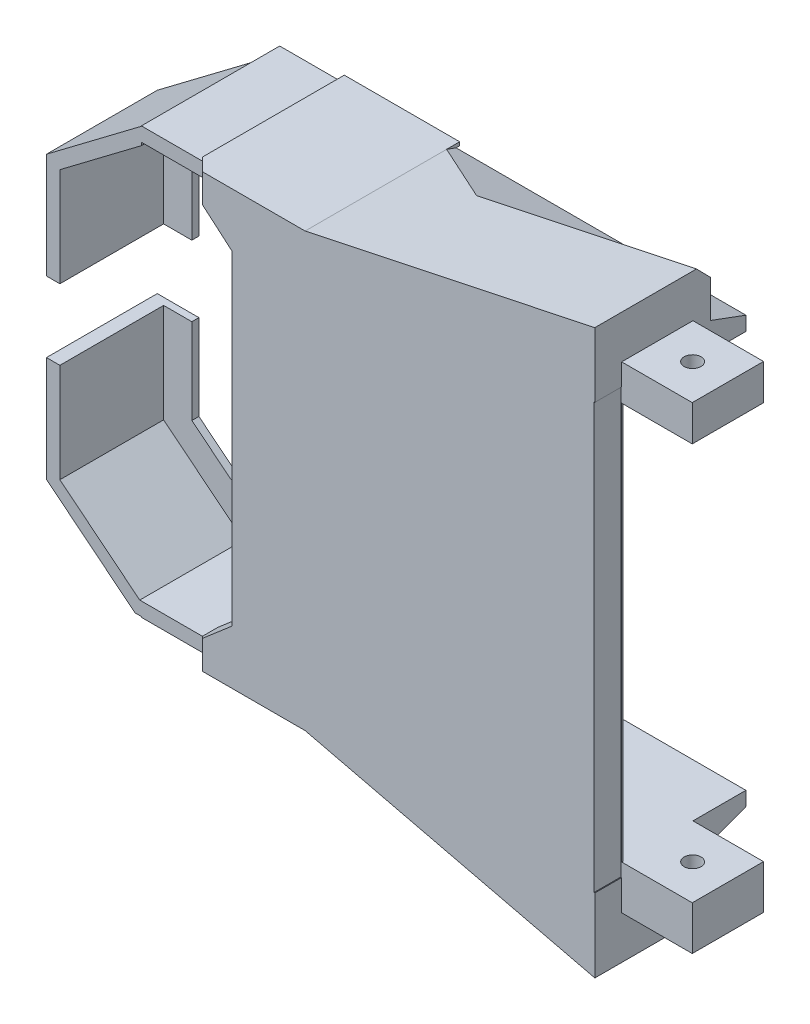
SolidWorks part; units mm, degrees
ref_plane "前视基准面" through (0, 0, 0) normal (0, 0, 1) x (1, 0, 0)
ref_plane "上视基准面" through (0, 0, 0) normal (0, 1, 0) x (1, 0, 0)
ref_plane "右视基准面" through (0, 0, 0) normal (1, 0, 0) x (0, 0, -1)
other "Configuration Table"
sketch "草图2" plane through (0, 0, 0) normal (0, 0, 1) x (1, 0, 0)
  line L0 (-79.35, 2) -> (-38.3, 2) construction
  line L1 (-104.35, 0) -> (-79.35, 0)
  line L2 (-104.35, 0) -> (-104.35, 2)
  line L3 (-104.35, 2) -> (-79.35, 2)
  line L4 (-104.35, 60.3) -> (-104.35, 0)
  line L5 (-104.35, 0) -> (-79.35, 0)
  line L6 (-79.35, 0) -> (-79.35, 6)
  line L7 (-79.35, 60.3) -> (-104.35, 60.3)
  line L8 (-104.35, 60.3) -> (-104.35, 0)
  line L9 (-104.35, 0) -> (-79.35, 0)
  line L10 (-79.35, 0) -> (-79.35, 6)
  line L11 (-79.35, 60.3) -> (-104.35, 60.3)
  line L12 (-79.35, 0) -> (-79.35, 2)
  line L13 (-38.3, 58.3) -> (-79.35, 58.3) construction
  line L14 (-104.35, 60.3) -> (-79.35, 60.3)
  line L15 (-104.35, 60.3) -> (-104.35, 58.3)
  line L16 (-104.35, 58.3) -> (-79.35, 58.3)
  line L17 (-79.35, 60.3) -> (-79.35, 58.3)
  line L34 (-98.35, 6) -> (-98.35, 54.3)
  line L35 (-98.35, 6) -> (-98.35, 54.3)
  line L36 (-98.35, 54.3) -> (-79.35, 54.3)
  line L37 (-98.35, 54.3) -> (-79.35, 54.3)
  line L38 (-79.35, 54.3) -> (-79.35, 60.3)
  line L39 (-79.35, 54.3) -> (-79.35, 60.3)
  line L40 (-79.35, 6) -> (-98.35, 6)
  line L41 (-79.35, 6) -> (-98.35, 6)
  line M9 (-104.35, 60.3) -> (-104.35, 0)
  line M10 (-104.35, 0) -> (-79.35, 0)
  line M11 (-79.35, 0) -> (-79.35, 6)
  line M12 (-79.35, 60.3) -> (-104.35, 60.3)
  dimension "D1" = 0
extrude "凸台-拉伸1" add sketch "草图2" along normal blind 15 contours L3 M9 M10 M11 | L16 L10 M9 M12
sketch "草图3" plane through (0, 0, 15) normal (0, 0, 1) x (1, 0, 0)
  line L0 (-104.45, -10.35) -> (-95.7, 0) construction
  line L1 (-91.85, 0) -> (-79.35, 0)
  line L2 (-91.85, 0) -> (-91.85, 60.3)
  line L3 (-91.85, 60.3) -> (-79.35, 60.3)
  line L4 (-104.35, 60.3) -> (-104.35, 58.3)
  line L5 (-104.35, 58.3) -> (-79.35, 58.3)
  line L6 (-79.35, 58.3) -> (-79.35, 60.3)
  line L7 (-79.35, 60.3) -> (-104.35, 60.3)
  line L8 (-104.35, 60.3) -> (-104.35, 58.3)
  line L9 (-104.35, 58.3) -> (-79.35, 58.3)
  line L11 (-79.35, 60.3) -> (-104.35, 60.3)
  line L12 (-79.35, 2) -> (-104.35, 2)
  line L13 (-104.35, 2) -> (-104.35, 0)
  line L14 (-104.35, 0) -> (-79.35, 0)
  line L15 (-79.35, 0) -> (-79.35, 2)
  line L16 (-79.35, 2) -> (-104.35, 2)
  line L17 (-104.35, 2) -> (-104.35, 0)
  line L18 (-104.35, 0) -> (-79.35, 0)
  line L19 (-79.35, 0) -> (-79.35, 2)
  line L20 (-79.35, 0) -> (-79.35, 60.3)
  line L21 (-91.85, 60.3) -> (-95.7, 60.3)
  line L22 (-91.85, 60.3) -> (-91.85, 0)
  line L23 (-91.85, 0) -> (-95.7, 0)
  line L24 (-95.7, 60.3) -> (-95.7, 0)
  line L29 (-79.35, 58.3) -> (-79.35, 60.3)
  dimension "D1" = 0
  dimension "D2" = 0
extrude "凸台-拉伸2" add sketch "草图3" along normal up to surface (2.6 mm away)
sketch "草图4" plane through (0, 0, 19.6) normal (0, 0, 1) x (1, 0, 0)
  line L0 (-104.5804, 2) -> (-115.8959, 11.1076)
  line L1 (-115.8959, 11.1076) -> (-115.8959, 49.1539)
  line L2 (-115.8959, 49.1539) -> (-103.7799, 58.3)
  line L3 (-103.7799, 58.3) -> (-91.3902, 58.3)
  line L4 (-91.3902, 58.3) -> (-103.5219, 72.65)
  line L5 (-103.5219, 72.65) -> (-148.2166, 72.65)
  line L6 (-148.2166, 72.65) -> (-165.6166, 67)
  line L7 (-165.6166, 67) -> (-170, 67)
  line L8 (-170, 67) -> (-170, -5.1533)
  line L9 (-170, -5.1533) -> (-163.6936, -18.35)
  line L10 (-163.6936, -18.35) -> (-140.104, -18.35)
  line L11 (-140.104, -18.35) -> (-136.104, -12.35)
  line L12 (-136.104, -12.35) -> (-103.5219, -12.35)
  line L13 (-103.5219, -12.35) -> (-91.3902, 2)
  line L14 (-91.3902, 2) -> (-104.5804, 2)
  line L15 (-117.8959, 50.15) -> (-104.45, 60.3)
  line L16 (-104.45, 60.3) -> (-95.7, 60.3)
  line L17 (-95.7, 60.3) -> (-104.45, 70.65)
  line L18 (-104.45, 70.65) -> (-147.9, 70.65)
  line L19 (-147.9, 70.65) -> (-165.3, 65)
  line L20 (-165.3, 65) -> (-168, 65)
  line L21 (-168, 65) -> (-168, -4.7)
  line L22 (-168, -4.7) -> (-162.4327, -16.35)
  line L23 (-162.4327, -16.35) -> (-141.1744, -16.35)
  line L24 (-141.1744, -16.35) -> (-137.1744, -10.35)
  line L25 (-137.1744, -10.35) -> (-104.45, -10.35)
  line L26 (-104.45, -10.35) -> (-95.7, 0)
  line L27 (-95.7, 0) -> (-105.2853, 0)
  line L28 (-105.2853, 0) -> (-117.8959, 10.15)
  line L29 (-117.8959, 10.15) -> (-117.8959, 50.15)
  line L30 (-117.8959, 50.15) -> (-104.45, 60.3)
  line L31 (-104.45, 60.3) -> (-95.7, 60.3)
  line L32 (-95.7, 60.3) -> (-104.45, 70.65)
  line L33 (-104.45, 70.65) -> (-147.9, 70.65)
  line L34 (-147.9, 70.65) -> (-165.3, 65)
  line L35 (-165.3, 65) -> (-168, 65)
  line L36 (-168, 65) -> (-168, -4.7)
  line L37 (-168, -4.7) -> (-162.4327, -16.35)
  line L38 (-162.4327, -16.35) -> (-141.1744, -16.35)
  line L39 (-141.1744, -16.35) -> (-137.1744, -10.35)
  line L40 (-137.1744, -10.35) -> (-104.45, -10.35)
  line L41 (-104.45, -10.35) -> (-95.7, 0)
  line L42 (-95.7, 0) -> (-105.2853, 0)
  line L43 (-105.2853, 0) -> (-117.8959, 10.15)
  line L44 (-117.8959, 10.15) -> (-117.8959, 50.15)
  line L45 (-104.35, 58.3) -> (-104.35, 57.8696)
  line L46 (-104.35, 0) -> (-104.35, 60.3) construction
  line L47 (-117.7959, 10.1979) -> (-117.7959, 50.1002)
  line L48 (-117.7959, 50.1002) -> (-104.4165, 60.2)
  line L49 (-104.4165, 60.2) -> (-95.4845, 60.2)
  line L50 (-95.4845, 60.2) -> (-104.4036, 70.75)
  line L51 (-104.4036, 70.75) -> (-147.9158, 70.75)
  line L52 (-147.9158, 70.75) -> (-165.3158, 65.1)
  line L53 (-79.35, 0) -> (-79.35, 60.3)
  line L54 (-79.35, 60.3) -> (-104.35, 60.3)
  line L55 (-104.35, 60.3) -> (-104.35, 58.3)
  line L56 (-104.35, 58.3) -> (-95.7, 58.3)
  line L57 (-95.7, 58.3) -> (-95.7, 2)
  line L58 (-95.7, 2) -> (-104.35, 2)
  line L59 (-104.35, 2) -> (-104.35, 0)
  line L60 (-104.35, 0) -> (-79.35, 0)
  line L61 (-79.35, 0) -> (-79.35, 60.3)
  line L62 (-79.35, 60.3) -> (-104.35, 60.3)
  line L63 (-104.35, 60.3) -> (-104.35, 58.3)
  line L64 (-104.35, 58.3) -> (-95.7, 58.3)
  line L65 (-95.7, 58.3) -> (-95.7, 2)
  line L66 (-95.7, 2) -> (-104.35, 2)
  line L67 (-104.35, 2) -> (-104.35, 0)
  line L68 (-104.35, 0) -> (-79.35, 0)
  line L69 (-165.3158, 65.1) -> (-168.1, 65.1)
  line L70 (-168.1, 65.1) -> (-168.1, -4.7227)
  line L71 (-168.1, -4.7227) -> (-162.4958, -16.45)
  line L72 (-162.4958, -16.45) -> (-141.1209, -16.45)
  line L73 (-141.1209, -16.45) -> (-137.1209, -10.45)
  line L74 (-137.1209, -10.45) -> (-104.4036, -10.45)
  line L75 (-104.4036, -10.45) -> (-95.4845, 0.1)
  line L76 (-95.4845, 0.1) -> (-105.2501, 0.1)
  line L77 (-105.2501, 0.1) -> (-117.7959, 10.1979)
  dimension "D1" = 0
  dimension "D2" = 2
  dimension "D3" = 0
  dimension "D4" = 0.1
extrude "凸台-拉伸3" add sketch "草图4" against normal offset from surface (15.7 mm away) 4 contours L77 L76 L67 L14 L0 L1 L2 L45 L63 L49 L48 L47
sketch "草图5" plane through (0, 0, 3.9) normal (0, 0, -1) x (-1, 0, 0)
  line L0 (104.35, 2) -> (104.35, 57.8696)
  line L12 (104.35, 0.1) -> (105.2501, 0.1)
  line L13 (105.2501, 0.1) -> (117.7959, 10.1979)
  line L14 (117.7959, 10.1979) -> (117.7959, 50.1002)
  line L15 (117.7959, 50.1002) -> (104.4165, 60.2)
  line L16 (104.4165, 60.2) -> (104.35, 60.2)
  line L17 (104.35, 60.2) -> (104.35, 58.3)
  line L18 (104.35, 58.3) -> (104.35, 57.8696)
  line L19 (104.35, 57.8696) -> (115.8959, 49.1539)
  line L20 (115.8959, 49.1539) -> (115.8959, 11.1076)
  line L21 (115.8959, 11.1076) -> (104.5804, 2)
  line L22 (104.5804, 2) -> (104.35, 2)
  line L23 (104.35, 2) -> (104.35, 0.1)
  line L24 (104.35, 0.1) -> (105.2501, 0.1)
  line L25 (105.2501, 0.1) -> (117.7959, 10.1979)
  line L26 (117.7959, 10.1979) -> (117.7959, 50.1002)
  line L27 (117.7959, 50.1002) -> (104.4165, 60.2)
  line L28 (104.4165, 60.2) -> (104.35, 60.2)
  line L29 (104.35, 60.2) -> (104.35, 58.3)
  line L30 (104.35, 58.3) -> (104.35, 57.8696)
  line L31 (104.35, 57.8696) -> (115.8959, 49.1539)
  line L32 (115.8959, 49.1539) -> (115.8959, 11.1076)
  line L33 (115.8959, 11.1076) -> (104.5804, 2)
  line L34 (104.5804, 2) -> (104.35, 2)
  line L35 (104.35, 2) -> (104.35, 0.1)
  line M21 (104.35, 57.8696) -> (115.8959, 49.1539)
  line M22 (115.8959, 49.1539) -> (115.8959, 11.1076)
  line M23 (115.8959, 11.1076) -> (104.5804, 2)
  line M24 (104.5804, 2) -> (104.35, 2)
  dimension "D1" = 0
extrude "凸台-拉伸4" add sketch "草图5" against normal blind 1 contours L0 M24 M23 M22 M21
sketch "草图6" plane through (-104.35, 0, 0) normal (1, 0, 0) x (0, 0, -1)
  line L0 (-4.9, 57.8696) -> (-4.9, 58.3)
  line L8 (-3.9, 2) -> (-3.9, 58.3)
  line L9 (-3.9, 58.3) -> (-17.6, 58.3)
  line L10 (-17.6, 58.3) -> (-17.6, 60.2)
  line L11 (-17.6, 60.2) -> (-19.6, 60.2)
  line L12 (-19.6, 60.2) -> (-19.6, 57.8696)
  line L13 (-19.6, 57.8696) -> (-4.9, 57.8696)
  line L14 (-4.9, 57.8696) -> (-4.9, 2)
  line L15 (-4.9, 2) -> (-3.9, 2)
  line L16 (-3.9, 2) -> (-3.9, 58.3)
  line L17 (-3.9, 58.3) -> (-17.6, 58.3)
  line L18 (-17.6, 58.3) -> (-17.6, 60.2)
  line L19 (-17.6, 60.2) -> (-19.6, 60.2)
  line L20 (-19.6, 60.2) -> (-19.6, 57.8696)
  line L21 (-19.6, 57.8696) -> (-4.9, 57.8696)
  line L22 (-4.9, 57.8696) -> (-4.9, 2)
  line L23 (-4.9, 2) -> (-3.9, 2)
  line M9 (-3.9, 2) -> (-3.9, 58.3)
  line M10 (-3.9, 58.3) -> (-17.6, 58.3)
  line M15 (-4.9, 57.8696) -> (-4.9, 2)
  line M16 (-4.9, 2) -> (-3.9, 2)
  dimension "D1" = 0
extrude "凸台-拉伸5" add sketch "草图6" along normal blind 2 contours L0 M15 M16 M9 M10
sketch "草图7" plane through (0, 0, 3.9) normal (0, 0, -1) x (-1, 0, 0)
  line L0 (104.35, 58.3) -> (104.35, 2)
  line L10 (104.35, 60.2) -> (104.35, 58.3)
  line L11 (104.35, 58.3) -> (102.35, 58.3)
  line L12 (102.35, 58.3) -> (102.35, 2)
  line L13 (102.35, 2) -> (104.35, 2)
  line L14 (104.35, 2) -> (104.35, 0.1)
  line L15 (104.35, 0.1) -> (105.2501, 0.1)
  line L16 (105.2501, 0.1) -> (117.7959, 10.1979)
  line L17 (117.7959, 10.1979) -> (117.7959, 50.1002)
  line L18 (117.7959, 50.1002) -> (104.4165, 60.2)
  line L19 (104.4165, 60.2) -> (104.35, 60.2)
  line L20 (104.35, 60.2) -> (104.35, 58.3)
  line L21 (104.35, 58.3) -> (102.35, 58.3)
  line L22 (102.35, 58.3) -> (102.35, 2)
  line L23 (102.35, 2) -> (104.35, 2)
  line L24 (104.35, 2) -> (104.35, 0.1)
  line L25 (104.35, 0.1) -> (105.2501, 0.1)
  line L26 (105.2501, 0.1) -> (117.7959, 10.1979)
  line L27 (117.7959, 10.1979) -> (117.7959, 50.1002)
  line L28 (117.7959, 50.1002) -> (104.4165, 60.2)
  line L29 (104.4165, 60.2) -> (104.35, 60.2)
  line M13 (104.35, 58.3) -> (102.35, 58.3)
  line M14 (102.35, 58.3) -> (102.35, 2)
  line M15 (102.35, 2) -> (104.35, 2)
  dimension "D1" = 0
extrude "凸台-拉伸6" add sketch "草图7" along normal up to surface (3.9 mm away) contours L0 M13 M14 M15 up to face at (-91.85, 1, 0)
sketch "草图8" plane through (0, 0, 0) normal (0, 0, -1) x (-1, 0, 0)
  line L0 (102.35, 58.3) -> (98.35, 54.3)
  line L1 (102.35, 58.3) -> (98.35, 58.3)
  line L2 (102.35, 58.3) -> (102.35, 54.3)
  line L3 (102.35, 54.3) -> (98.35, 54.3)
  line L4 (98.35, 58.3) -> (98.35, 54.3)
  line L5 (102.35, 2) -> (98.35, 2)
  line L6 (102.35, 2) -> (102.35, 6)
  line L7 (102.35, 6) -> (98.35, 6)
  line L8 (104.35, 0) -> (104.35, 60.3)
  line L9 (104.35, 60.3) -> (79.35, 60.3)
  line L10 (79.35, 60.3) -> (79.35, 58.3)
  line L11 (79.35, 58.3) -> (102.35, 58.3)
  line L12 (102.35, 58.3) -> (102.35, 2)
  line L13 (102.35, 2) -> (79.35, 2)
  line L14 (79.35, 2) -> (79.35, 0)
  line L15 (79.35, 0) -> (104.35, 0)
  line L16 (104.35, 0) -> (104.35, 60.3)
  line L17 (104.35, 60.3) -> (79.35, 60.3)
  line L18 (79.35, 60.3) -> (79.35, 58.3)
  line L19 (79.35, 58.3) -> (102.35, 58.3)
  line L20 (102.35, 58.3) -> (102.35, 2)
  line L21 (102.35, 2) -> (79.35, 2)
  line L22 (79.35, 2) -> (79.35, 0)
  line L23 (79.35, 0) -> (104.35, 0)
  line L24 (98.35, 2) -> (98.35, 6)
  line L25 (102.35, 6) -> (98.35, 2)
  line L26 (79.35, 60.3) -> (79.35, 0)
  line L27 (104.35, 60.3) -> (79.35, 60.3)
  line L28 (104.35, 60.2) -> (104.35, 60.3)
  line L29 (104.35, 58.3) -> (104.35, 60.2)
  line L30 (95.7, 58.3) -> (104.35, 58.3)
  line L31 (95.7, 2) -> (95.7, 58.3)
  line L32 (104.35, 2) -> (95.7, 2)
  line L33 (104.35, 0.1) -> (104.35, 2)
  line L34 (104.35, 0) -> (104.35, 0.1)
  line L35 (79.35, 0) -> (104.35, 0)
  line L36 (79.35, 60.3) -> (79.35, 0)
  line L37 (104.35, 60.3) -> (79.35, 60.3)
  line L38 (104.35, 60.2) -> (104.35, 60.3)
  line L39 (104.35, 58.3) -> (104.35, 60.2)
  line L40 (95.7, 58.3) -> (104.35, 58.3)
  line L41 (95.7, 2) -> (95.7, 58.3)
  line L42 (104.35, 2) -> (95.7, 2)
  line L43 (104.35, 0.1) -> (104.35, 2)
  line L44 (104.35, 0) -> (104.35, 0.1)
  line L45 (79.35, 0) -> (104.35, 0)
  circle A0 centre (100.35, 56.3) radius 1.2
  circle A1 centre (100.35, 4) radius 1.2
  line M26 (79.35, 58.3) -> (102.35, 58.3)
  line M27 (102.35, 58.3) -> (102.35, 2)
  line M28 (102.35, 2) -> (79.35, 2)
  dimension "D7" = 2.4
  dimension "D8" = 2.4
  dimension "D3" = 4
  dimension "D4" = 4
  dimension "D5" = 4
  dimension "D6" = 4
  dimension "D1" = 0
  dimension "D2" = 0
extrude "凸台-拉伸7" add sketch "草图8" against normal blind 2 contours A1 L25 L7 L24 | A1 L25 M28 M27 | A0 L0 L4 M26 | A0 L0 L3 M27
sketch "草图9" plane through (-79.35, 0, 0) normal (1, 0, 0) x (0, 0, -1)
  line L0 (-18.1, -0.5) -> (0.5, -0.5)
  line L1 (0.5, -0.5) -> (0.5, 0)
  line L5 (0.5, 60.3) -> (0.5, 60.8)
  line L6 (0.5, 60.8) -> (-18.1, 60.8)
  line L8 (0, 0) -> (0, 2)
  line L9 (0, 2) -> (-15, 2)
  line L10 (-15, 2) -> (-15, 58.3)
  line L11 (-15, 58.3) -> (0, 58.3)
  line L12 (0, 58.3) -> (0, 60.3)
  line L13 (0, 60.3) -> (-17.6, 60.3)
  line L14 (-17.6, 60.3) -> (-17.6, 0)
  line L15 (-17.6, 0) -> (0, 0)
  line L21 (0, 60.3) -> (-17.6, 60.3)
  line L23 (-17.6, 0) -> (0, 0)
  line L24 (-17.6, -0.5) -> (-17.6, 0)
  line L25 (-17.6, 60.3) -> (-17.6, 60.8)
  line L26 (0, 0) -> (0.5, 0)
  line L27 (0, 60.3) -> (0.5, 60.3)
  line L28 (0.5, 57.8) -> (0.5, 60.8) construction
  line L29 (-18.1, 60.8) -> (-18.1, -0.5) construction
  line L30 (-17.6, 60.3) -> (-17.6, 0) construction
  line L31 (-15, 2) -> (-15, 58.3) construction
  line L32 (-14.5, 2.5) -> (-14.5, 57.8) construction
  line L33 (-14.5, 57.8) -> (0.5, 57.8) construction
  line L34 (-15, 58.3) -> (0, 58.3) construction
  line L35 (0, 58.3) -> (0, 60.3) construction
  line L36 (0.5, 2.5) -> (-14.5, 2.5) construction
  line L37 (0, 2) -> (-15, 2) construction
  line L38 (0, 0) -> (0, 2) construction
  line L39 (0.5, -0.5) -> (0.5, 2.5) construction
  line M22 (0, 60.3) -> (-17.6, 60.3)
  line M24 (-17.6, 0) -> (0, 0)
  dimension "D1" = 0
  dimension "D2" = 0.5
extrude "凸台-拉伸8" add sketch "草图9" against normal up to vertex (16.7727 mm away) contours L26 L24 L0 L1 M24 | L27 L5 L6 L25 M22
sketch "草图10" plane through (0, 0, 17.6) normal (0, 0, 1) x (1, 0, 0)
  line L0 (-89.7, 7.15) -> (-89.7, 53.15)
  line L1 (-95.7, 2) -> (-89.7, 2)
  line L2 (-95.7, 2) -> (-95.7, 58.3)
  line L3 (-95.7, 58.3) -> (-89.7, 58.3)
  line L4 (-89.7, 2) -> (-89.7, 58.3)
  line L5 (-95.7, 2) -> (-89.7, 7.15)
  line L6 (-95.7, 58.3) -> (-89.7, 53.15)
  line L14 (-79.35, -0.5) -> (-79.35, 60.8)
  line L15 (-79.35, 60.8) -> (-95.7, 60.8)
  line L16 (-95.7, 60.8) -> (-95.7, 60.3)
  line L17 (-95.7, 60.3) -> (-104.35, 60.3)
  line L18 (-104.35, 60.3) -> (-104.35, 60.2)
  line L19 (-104.35, 60.2) -> (-104.35, 58.3)
  line L20 (-104.35, 58.3) -> (-95.7, 58.3)
  line L21 (-95.7, 58.3) -> (-95.7, 2)
  line L22 (-95.7, 2) -> (-104.35, 2)
  line L23 (-104.35, 2) -> (-104.35, 0.1)
  line L24 (-104.35, 0.1) -> (-104.35, 0)
  line L25 (-104.35, 0) -> (-95.7, 0)
  line L26 (-95.7, 0) -> (-95.7, -0.5)
  line L27 (-95.7, -0.5) -> (-79.35, -0.5)
  line L28 (-79.35, -0.5) -> (-79.35, 60.8)
  line L29 (-79.35, 60.8) -> (-95.7, 60.8)
  line L30 (-95.7, 60.8) -> (-95.7, 60.3)
  line L31 (-95.7, 60.3) -> (-104.35, 60.3)
  line L32 (-104.35, 60.3) -> (-104.35, 60.2)
  line L33 (-104.35, 60.2) -> (-104.35, 58.3)
  line L34 (-104.35, 58.3) -> (-95.7, 58.3)
  line L35 (-95.7, 58.3) -> (-95.7, 2)
  line L36 (-95.7, 2) -> (-104.35, 2)
  line L37 (-104.35, 2) -> (-104.35, 0.1)
  line L38 (-104.35, 0.1) -> (-104.35, 0)
  line L39 (-104.35, 0) -> (-95.7, 0)
  line L40 (-95.7, 0) -> (-95.7, -0.5)
  line L41 (-95.7, -0.5) -> (-79.35, -0.5)
  point P12 (-89.7, 30.15)
  line M26 (-95.7, 58.3) -> (-95.7, 2)
  dimension "D2" = 6
  dimension "D3" = 46
  dimension "D1" = 0
extrude "切除-拉伸1" cut sketch "草图10" against normal up to surface (2.6 mm away) contours L6 L5 L0 M26 up to face at (-87.525, 30.15, 15)
sketch "草图11" plane through (-79.35, 0, 0) normal (1, 0, 0) x (0, 0, -1)
  line L0 (0, 0) -> (-17.6, 0.1)
  line L1 (0, 60.3) -> (-17.6, 60.3)
  line L12 (0, 0) -> (0, 2)
  line L13 (0, 2) -> (-15, 2)
  line L14 (-15, 2) -> (-15, 58.3)
  line L15 (-15, 58.3) -> (0, 58.3)
  line L16 (0, 58.3) -> (0, 60.3)
  line L17 (0, 60.3) -> (0.5, 60.3)
  line L18 (0.5, 60.3) -> (0.5, 60.8)
  line L19 (0.5, 60.8) -> (-17.6, 60.8)
  line L20 (-17.6, 60.8) -> (-17.6, -0.5)
  line L21 (-17.6, -0.5) -> (0.5, -0.5)
  line L22 (0.5, -0.5) -> (0.5, 0)
  line L23 (0.5, 0) -> (0, 0)
  line L24 (0, 0) -> (0, 2)
  line L25 (0, 2) -> (-15, 2)
  line L26 (-15, 2) -> (-15, 58.3)
  line L27 (-15, 58.3) -> (0, 58.3)
  line L28 (0, 58.3) -> (0, 60.3)
  line L29 (0, 60.3) -> (0.5, 60.3)
  line L30 (0.5, 60.3) -> (0.5, 60.8)
  line L31 (0.5, 60.8) -> (-17.6, 60.8)
  line L32 (-17.6, 60.8) -> (-17.6, -0.5)
  line L33 (-17.6, -0.5) -> (0.5, -0.5)
  line L34 (0.5, -0.5) -> (0.5, 0)
  line L35 (0.5, 0) -> (0, 0)
  line M13 (0, 0) -> (0, 2)
  line M14 (0, 2) -> (-15, 2)
  line M15 (-15, 2) -> (-15, 58.3)
  line M16 (-15, 58.3) -> (0, 58.3)
  line M17 (0, 58.3) -> (0, 60.3)
  line M21 (-17.6, 60.8) -> (-17.6, -0.5)
  dimension "D1" = 0
extrude "凸台-拉伸9" add sketch "草图11" along normal up to surface (41.05 mm away) contours L1 L0 M17 M21 M13 M14 M15 M16
sketch "草图12" plane through (-38.3, 0, 0) normal (1, 0, 0) x (0, 0, -1)
  line L0 (-7.4, 57.65) -> (-7.4, 63.47) construction
  line L1 (-7.4, 57.65) -> (-7.4, 63.47)
  line L2 (-7.4, 57.65) -> (-7.4, 0.042)
  line L3 (-7.4, -4.33) -> (-7.4, 63.47) construction
  line L4 (-7.4, 63.47) -> (-19.4, 63.47) construction
  line L5 (-7.4, 63.47) -> (-19.4, 63.47)
  line L6 (-19.4, -4.33) -> (-7.4, -4.33) construction
  line L7 (-19.4, -4.33) -> (-7.4, -4.33)
  line L8 (0, 60.3) -> (-17.6, 60.3)
  line L9 (-17.6, 60.3) -> (-17.6, 0.1)
  line L10 (-17.6, 0.1) -> (0, 0)
  line L11 (0, 0) -> (0, 2)
  line L12 (0, 2) -> (-15, 2)
  line L13 (-15, 2) -> (-15, 58.3)
  line L14 (-15, 58.3) -> (0, 58.3)
  line L15 (0, 58.3) -> (0, 60.3)
  line L16 (0, 60.3) -> (-17.6, 60.3)
  line L17 (-17.6, 60.3) -> (-17.6, 0.1)
  line L18 (-17.6, 0.1) -> (0, 0)
  line L19 (0, 0) -> (0, 2)
  line L20 (0, 2) -> (-15, 2)
  line L21 (-15, 2) -> (-15, 58.3)
  line L22 (-15, 58.3) -> (0, 58.3)
  line L23 (0, 58.3) -> (0, 60.3)
  line L24 (-17.6, 60.3) -> (-17.6, 63.47)
  line L25 (-17.6, 0.1) -> (-17.6, -4.33)
  line L26 (-7.4, -4.33) -> (-7.4, 57.65)
  line L27 (-19.4, -4.23) -> (-7.5, -4.23)
  line L28 (-7.5, -4.23) -> (-7.5, 57.65)
  line L29 (-7.5, 57.65) -> (-7.5, 63.37)
  line L30 (-7.5, 63.37) -> (-19.4, 63.37)
  line L31 (-15, 58.3) -> (-17.6, 58.3)
  line L32 (-15, 2) -> (-17.6, 2)
  line M13 (-17.6, 60.3) -> (-17.6, 0.1)
  line M14 (-17.6, 0.1) -> (0, 0)
  line M18 (-15, 58.3) -> (0, 58.3)
  dimension "D1" = 0
  dimension "D2" = 0.1
extrude "凸台-拉伸10" add sketch "草图12" along normal blind 10 contours L20 L32 L28 M13 M14 | L27 L28 L25 M14 | L29 L30 L24 L16 | L31 L29 L16 M18 M13
sketch "草图13" plane through (0, 58.3, 0) normal (0, -1, 0) x (1, 0, 0)
  line L0 (-38.3, 17.6) -> (-28.3, 7.5)
  line L14 (-102.35, 2) -> (-98.35, 2)
  line L15 (-98.35, 2) -> (-98.35, 0)
  line L16 (-98.35, 0) -> (-38.3, 0)
  line L17 (-38.3, 0) -> (-38.3, 7.5)
  line L18 (-38.3, 7.5) -> (-28.3, 7.5)
  line L19 (-28.3, 7.5) -> (-28.3, 17.6)
  line L20 (-28.3, 17.6) -> (-38.3, 17.6)
  line L21 (-38.3, 17.6) -> (-38.3, 15)
  line L22 (-38.3, 15) -> (-95.7, 15)
  line L23 (-95.7, 15) -> (-95.7, 17.6)
  line L24 (-95.7, 17.6) -> (-104.35, 17.6)
  line L25 (-104.35, 17.6) -> (-104.35, 4.9)
  line L26 (-104.35, 4.9) -> (-102.35, 4.9)
  line L27 (-102.35, 4.9) -> (-102.35, 2)
  line L28 (-102.35, 2) -> (-98.35, 2)
  line L29 (-98.35, 2) -> (-98.35, 0)
  line L30 (-98.35, 0) -> (-38.3, 0)
  line L31 (-38.3, 0) -> (-38.3, 7.5)
  line L32 (-38.3, 7.5) -> (-28.3, 7.5)
  line L33 (-28.3, 7.5) -> (-28.3, 17.6)
  line L34 (-28.3, 17.6) -> (-38.3, 17.6)
  line L35 (-38.3, 17.6) -> (-38.3, 15)
  line L36 (-38.3, 15) -> (-95.7, 15)
  line L37 (-95.7, 15) -> (-95.7, 17.6)
  line L38 (-95.7, 17.6) -> (-104.35, 17.6)
  line L39 (-104.35, 17.6) -> (-104.35, 4.9)
  line L40 (-104.35, 4.9) -> (-102.35, 4.9)
  line L41 (-102.35, 4.9) -> (-102.35, 2)
  circle A0 centre (-33.3, 12.55) radius 1.2
  dimension "D2" = 2.4
  dimension "D1" = 0
extrude "切除-拉伸2" cut sketch "草图13" against normal through all and the other way through all contours L0 A0 | L0 A0
sketch "草图14" plane through (0, 0, 17.6) normal (0, 0, 1) x (1, 0, 0)
  line L0 (-38.3, 0.1) -> (-38.3, 2)
  line L1 (-38.3, 58.3) -> (-38.3, 60.3)
  line L2 (-38.42, 58.3) -> (-38.42, 60.3)
  line L3 (-38.42, 2) -> (-38.42, 58.3)
  line L4 (-38.42, 0.1) -> (-38.42, 2)
  line L28 (-104.35, 58.3) -> (-95.7, 58.3)
  line L29 (-95.7, 58.3) -> (-89.7, 53.15)
  line L30 (-89.7, 53.15) -> (-89.7, 7.15)
  line L31 (-89.7, 7.15) -> (-95.7, 2)
  line L32 (-95.7, 2) -> (-104.35, 2)
  line L33 (-104.35, 2) -> (-104.35, 0.1)
  line L34 (-104.35, 0.1) -> (-104.35, 0)
  line L35 (-104.35, 0) -> (-95.7, 0)
  line L36 (-95.7, 0) -> (-95.7, -0.5)
  line L37 (-95.7, -0.5) -> (-79.35, -0.5)
  line L38 (-79.35, -0.5) -> (-79.35, 0.1)
  line L39 (-79.35, 0.1) -> (-38.3, 0.1)
  line L40 (-38.3, 0.1) -> (-38.3, -4.23)
  line L41 (-38.3, -4.23) -> (-28.3, -4.23)
  line L42 (-28.3, -4.23) -> (-28.3, 2)
  line L43 (-28.3, 2) -> (-38.3, 2)
  line L44 (-38.3, 2) -> (-38.3, 58.3)
  line L45 (-38.3, 58.3) -> (-28.3, 58.3)
  line L46 (-28.3, 58.3) -> (-28.3, 63.37)
  line L47 (-28.3, 63.37) -> (-38.3, 63.37)
  line L48 (-38.3, 63.37) -> (-38.3, 60.3)
  line L49 (-38.3, 60.3) -> (-79.35, 60.3)
  line L50 (-79.35, 60.3) -> (-79.35, 60.8)
  line L51 (-79.35, 60.8) -> (-95.7, 60.8)
  line L52 (-95.7, 60.8) -> (-95.7, 60.3)
  line L53 (-95.7, 60.3) -> (-104.35, 60.3)
  line L54 (-104.35, 60.3) -> (-104.35, 60.2)
  line L55 (-104.35, 60.2) -> (-104.35, 58.3)
  line L56 (-104.35, 58.3) -> (-95.7, 58.3)
  line L57 (-95.7, 58.3) -> (-89.7, 53.15)
  line L58 (-89.7, 53.15) -> (-89.7, 7.15)
  line L59 (-89.7, 7.15) -> (-95.7, 2)
  line L60 (-95.7, 2) -> (-104.35, 2)
  line L61 (-104.35, 2) -> (-104.35, 0.1)
  line L62 (-104.35, 0.1) -> (-104.35, 0)
  line L63 (-104.35, 0) -> (-95.7, 0)
  line L64 (-95.7, 0) -> (-95.7, -0.5)
  line L65 (-95.7, -0.5) -> (-79.35, -0.5)
  line L66 (-79.35, -0.5) -> (-79.35, 0.1)
  line L67 (-79.35, 0.1) -> (-38.3, 0.1)
  line L68 (-38.3, 0.1) -> (-38.3, -4.23)
  line L69 (-38.3, -4.23) -> (-28.3, -4.23)
  line L70 (-28.3, -4.23) -> (-28.3, 2)
  line L71 (-28.3, 2) -> (-38.3, 2)
  line L72 (-38.3, 2) -> (-38.3, 58.3)
  line L73 (-38.3, 58.3) -> (-28.3, 58.3)
  line L74 (-28.3, 58.3) -> (-28.3, 63.37)
  line L75 (-28.3, 63.37) -> (-38.3, 63.37)
  line L76 (-38.3, 63.37) -> (-38.3, 60.3)
  line L77 (-38.3, 60.3) -> (-79.35, 60.3)
  line L78 (-79.35, 60.3) -> (-79.35, 60.8)
  line L79 (-79.35, 60.8) -> (-95.7, 60.8)
  line L80 (-95.7, 60.8) -> (-95.7, 60.3)
  line L81 (-95.7, 60.3) -> (-104.35, 60.3)
  line L82 (-104.35, 60.3) -> (-104.35, 60.2)
  line L83 (-104.35, 60.2) -> (-104.35, 58.3)
  line M30 (-104.35, 58.3) -> (-95.7, 58.3)
  line M31 (-95.7, 58.3) -> (-89.7, 53.15)
  line M32 (-89.7, 53.15) -> (-89.7, 7.15)
  line M33 (-89.7, 7.15) -> (-95.7, 2)
  line M34 (-95.7, 2) -> (-104.35, 2)
  line M35 (-104.35, 2) -> (-104.35, 0.1)
  line M36 (-104.35, 0.1) -> (-104.35, 0)
  line M37 (-104.35, 0) -> (-95.7, 0)
  line M38 (-95.7, 0) -> (-95.7, -0.5)
  line M39 (-95.7, -0.5) -> (-79.35, -0.5)
  line M40 (-79.35, -0.5) -> (-79.35, 0.1)
  line M41 (-79.35, 0.1) -> (-38.3, 0.1)
  line M51 (-38.3, 60.3) -> (-79.35, 60.3)
  line M52 (-79.35, 60.3) -> (-79.35, 60.8)
  line M53 (-79.35, 60.8) -> (-95.7, 60.8)
  line M54 (-95.7, 60.8) -> (-95.7, 60.3)
  line M55 (-95.7, 60.3) -> (-104.35, 60.3)
  line M56 (-104.35, 60.3) -> (-104.35, 60.2)
  line M57 (-104.35, 60.2) -> (-104.35, 58.3)
  dimension "D1" = 0
  dimension "D2" = 0.12
extrude "凸台-拉伸11" add sketch "草图14" along normal up to surface (3.8 mm away) contours L4 L3 L2 M41 M51 M52 M53 M54 M55 M56 M57 M30 M31 M32 M33 M34 M35 M36 M37 M38 M39 M40
sketch "草图15" plane through (0, 0, 21.4) normal (0, 0, 1) x (1, 0, 0)
  line L0 (-95.7, 0) -> (-95.7, 2)
  line L1 (-95.7, 58.3) -> (-95.7, 60.3)
  line L18 (-79.35, -0.5) -> (-79.35, 0.1)
  line L19 (-79.35, 0.1) -> (-38.42, 0.1)
  line L20 (-38.42, 0.1) -> (-38.42, 60.3)
  line L21 (-38.42, 60.3) -> (-79.35, 60.3)
  line L22 (-79.35, 60.3) -> (-79.35, 60.8)
  line L23 (-79.35, 60.8) -> (-95.7, 60.8)
  line L24 (-95.7, 60.8) -> (-95.7, 60.3)
  line L25 (-95.7, 60.3) -> (-104.35, 60.3)
  line L26 (-104.35, 60.3) -> (-104.35, 58.3)
  line L27 (-104.35, 58.3) -> (-95.7, 58.3)
  line L28 (-95.7, 58.3) -> (-89.7, 53.15)
  line L29 (-89.7, 53.15) -> (-89.7, 7.15)
  line L30 (-89.7, 7.15) -> (-95.7, 2)
  line L31 (-95.7, 2) -> (-104.35, 2)
  line L32 (-104.35, 2) -> (-104.35, 0)
  line L33 (-104.35, 0) -> (-95.7, 0)
  line L34 (-95.7, 0) -> (-95.7, -0.5)
  line L35 (-95.7, -0.5) -> (-79.35, -0.5)
  line L36 (-79.35, -0.5) -> (-79.35, 0.1)
  line L37 (-79.35, 0.1) -> (-38.42, 0.1)
  line L38 (-38.42, 0.1) -> (-38.42, 60.3)
  line L39 (-38.42, 60.3) -> (-79.35, 60.3)
  line L40 (-79.35, 60.3) -> (-79.35, 60.8)
  line L41 (-79.35, 60.8) -> (-95.7, 60.8)
  line L42 (-95.7, 60.8) -> (-95.7, 60.3)
  line L43 (-95.7, 60.3) -> (-104.35, 60.3)
  line L44 (-104.35, 60.3) -> (-104.35, 58.3)
  line L45 (-104.35, 58.3) -> (-95.7, 58.3)
  line L46 (-95.7, 58.3) -> (-89.7, 53.15)
  line L47 (-89.7, 53.15) -> (-89.7, 7.15)
  line L48 (-89.7, 7.15) -> (-95.7, 2)
  line L49 (-95.7, 2) -> (-104.35, 2)
  line L50 (-104.35, 2) -> (-104.35, 0)
  line L51 (-104.35, 0) -> (-95.7, 0)
  line L52 (-95.7, 0) -> (-95.7, -0.5)
  line L53 (-95.7, -0.5) -> (-79.35, -0.5)
  line M27 (-95.7, 60.3) -> (-104.35, 60.3)
  line M28 (-104.35, 60.3) -> (-104.35, 58.3)
  line M29 (-104.35, 58.3) -> (-95.7, 58.3)
  line M33 (-95.7, 2) -> (-104.35, 2)
  line M34 (-104.35, 2) -> (-104.35, 0)
  line M35 (-104.35, 0) -> (-95.7, 0)
  dimension "D1" = 0
extrude "切除-拉伸3" cut sketch "草图15" against normal up to surface (1.8 mm away) contours L1 M29 M27 M28 | L0 M35 M33 M34 up to face at (-108.6151, 30.1108, 19.6)
sketch "草图16" plane through (0, 0, 15) normal (0, 0, -1) x (-1, 0, 0)
  line L6 (89.7, 53.15) -> (95.7, 58.3)
  line L7 (95.7, 58.3) -> (38.3, 58.3)
  line L8 (38.3, 58.3) -> (38.3, 2)
  line L9 (38.3, 2) -> (95.7, 2)
  line L10 (95.7, 2) -> (89.7, 7.15)
  line L11 (89.7, 7.15) -> (89.7, 53.15)
  line L12 (89.7, 53.15) -> (95.7, 58.3)
  line L13 (95.7, 58.3) -> (38.3, 58.3)
  line L14 (38.3, 58.3) -> (38.3, 2)
  line L15 (38.3, 2) -> (95.7, 2)
  line L16 (95.7, 2) -> (89.7, 7.15)
  line L17 (89.7, 7.15) -> (89.7, 53.15)
  dimension "D1" = 0
extrude "切除-拉伸4" cut sketch "草图16" against normal offset from surface (2.4 mm away) 4 up to face at (-79.7033, 30.1667, 21.4)
sketch "草图17" plane through (0, 0, 21.4) normal (0, 0, 1) x (1, 0, 0)
  line L0 (-38.3, -10.33) -> (-16.4, -10.33) construction
  line L1 (-38.3, -10.33) -> (-16.4, -10.33)
  line L2 (-79.35, -0.5) -> (-38.3, -10.33)
  line L3 (-79.35, 60.8) -> (-38.3, 69.47)
  line L4 (-38.42, 0.1) -> (-38.3, 0.1)
  line L5 (-38.42, 60.3) -> (-38.3, 60.3)
  line L12 (-95.7, 60.8) -> (-95.7, 58.3)
  line L13 (-95.7, 58.3) -> (-89.7, 53.15)
  line L14 (-89.7, 53.15) -> (-89.7, 7.15)
  line L15 (-89.7, 7.15) -> (-95.7, 2)
  line L16 (-95.7, 2) -> (-95.7, -0.5)
  line L17 (-95.7, -0.5) -> (-79.35, -0.5)
  line L18 (-79.35, -0.5) -> (-79.35, 0.1)
  line L19 (-79.35, 0.1) -> (-38.42, 0.1)
  line L20 (-38.42, 0.1) -> (-38.42, 60.3)
  line L21 (-38.42, 60.3) -> (-79.35, 60.3)
  line L22 (-79.35, 60.3) -> (-79.35, 60.8)
  line L23 (-79.35, 60.8) -> (-95.7, 60.8)
  line L24 (-95.7, 60.8) -> (-95.7, 58.3)
  line L25 (-95.7, 58.3) -> (-89.7, 53.15)
  line L26 (-89.7, 53.15) -> (-89.7, 7.15)
  line L27 (-89.7, 7.15) -> (-95.7, 2)
  line L28 (-95.7, 2) -> (-95.7, -0.5)
  line L29 (-95.7, -0.5) -> (-79.35, -0.5)
  line L30 (-79.35, -0.5) -> (-79.35, 0.1)
  line L31 (-79.35, 0.1) -> (-38.42, 0.1)
  line L32 (-38.42, 0.1) -> (-38.42, 60.3)
  line L33 (-38.42, 60.3) -> (-79.35, 60.3)
  line L34 (-79.35, 60.3) -> (-79.35, 60.8)
  line L35 (-79.35, 60.8) -> (-95.7, 60.8)
  line L38 (-16.4, 69.47) -> (-38.3, 69.47)
  line L39 (-38.3, 69.47) -> (-38.3, -10.33)
  line L40 (-38.3, -10.33) -> (-16.4, -10.33)
  line L41 (-16.4, -10.33) -> (-12.4, -6.33)
  line L42 (-12.4, -6.33) -> (37.42, -6.33)
  line L43 (37.42, -6.33) -> (41.42, -10.33)
  line L44 (41.42, -10.33) -> (49.42, -10.33)
  line L45 (49.42, -10.33) -> (49.42, 69.47)
  line L46 (49.42, 69.47) -> (41.42, 69.47)
  line L47 (41.42, 69.47) -> (37.42, 65.47)
  line L48 (37.42, 65.47) -> (-12.4, 65.47)
  line L49 (-12.4, 65.47) -> (-16.4, 69.47)
  line L50 (-16.4, 69.47) -> (-38.3, 69.47)
  line L51 (-38.3, 69.47) -> (-38.3, -10.33)
  line L52 (-38.3, -10.33) -> (-16.4, -10.33)
  line L53 (-16.4, -10.33) -> (-12.4, -6.33)
  line L54 (-12.4, -6.33) -> (37.42, -6.33)
  line L55 (37.42, -6.33) -> (41.42, -10.33)
  line L56 (41.42, -10.33) -> (49.42, -10.33)
  line L57 (49.42, -10.33) -> (49.42, 69.47)
  line L58 (49.42, 69.47) -> (41.42, 69.47)
  line L59 (41.42, 69.47) -> (37.42, 65.47)
  line L60 (37.42, 65.47) -> (-12.4, 65.47)
  line L61 (-12.4, 65.47) -> (-16.4, 69.47)
  line M32 (-79.35, -0.5) -> (-79.35, 0.1)
  line M33 (-79.35, 0.1) -> (-38.42, 0.1)
  line M35 (-38.42, 60.3) -> (-79.35, 60.3)
  line M36 (-79.35, 60.3) -> (-79.35, 60.8)
  dimension "D1" = 0
  dimension "D2" = 0
extrude "凸台-拉伸12" add sketch "草图17" against normal up to surface (16.4 mm away) contours L51 L3 L5 M36 M35 | L51 L4 L2 M33 M32
sketch "草图18" plane through (-38.3, 0, 0) normal (1, 0, 0) x (0, 0, -1)
  line L0 (-5, -1.85) -> (0, 0) construction
  line L1 (-5, -1.85) -> (0, 0)
  line L2 (0, 60.3) -> (-5, 62.15) construction
  line L3 (0, 60.3) -> (-5, 62.15)
  line L10 (-7.5, 63.37) -> (-7.5, 58.3)
  line L11 (-7.5, 58.3) -> (0, 58.3)
  line L12 (0, 58.3) -> (0, 60.3)
  line L13 (0, 60.3) -> (-5, 60.3)
  line L14 (-5, 60.3) -> (-5, 69.47)
  line L15 (-5, 69.47) -> (-21.4, 69.47)
  line L16 (-21.4, 69.47) -> (-21.4, 60.3)
  line L17 (-21.4, 60.3) -> (-17.6, 60.3)
  line L18 (-17.6, 60.3) -> (-17.6, 63.37)
  line L19 (-17.6, 63.37) -> (-7.5, 63.37)
  line L20 (-7.5, 63.37) -> (-7.5, 58.3)
  line L21 (-7.5, 58.3) -> (0, 58.3)
  line L22 (0, 58.3) -> (0, 60.3)
  line L23 (0, 60.3) -> (-5, 60.3)
  line L24 (-5, 60.3) -> (-5, 69.47)
  line L25 (-5, 69.47) -> (-21.4, 69.47)
  line L26 (-21.4, 69.47) -> (-21.4, 60.3)
  line L27 (-21.4, 60.3) -> (-17.6, 60.3)
  line L28 (-17.6, 60.3) -> (-17.6, 63.37)
  line L29 (-17.6, 63.37) -> (-7.5, 63.37)
  line L30 (0, 2) -> (-7.5, 2)
  line L31 (-7.5, 2) -> (-7.5, -4.23)
  line L32 (-7.5, -4.23) -> (-17.6, -4.23)
  line L33 (-17.6, -4.23) -> (-17.6, 0.1)
  line L34 (-17.6, 0.1) -> (-21.4, 0.1)
  line L35 (-21.4, 0.1) -> (-21.4, -10.33)
  line L36 (-21.4, -10.33) -> (-5, -10.33)
  line L37 (-5, -10.33) -> (-5, 0.0284)
  line L38 (-5, 0.0284) -> (0, 0)
  line L39 (0, 0) -> (0, 2)
  line L40 (0, 2) -> (-7.5, 2)
  line L41 (-7.5, 2) -> (-7.5, -4.23)
  line L42 (-7.5, -4.23) -> (-17.6, -4.23)
  line L43 (-17.6, -4.23) -> (-17.6, 0.1)
  line L44 (-17.6, 0.1) -> (-21.4, 0.1)
  line L45 (-21.4, 0.1) -> (-21.4, -10.33)
  line L46 (-21.4, -10.33) -> (-5, -10.33)
  line L47 (-5, -10.33) -> (-5, 0.0284)
  line L48 (-5, 0.0284) -> (0, 0)
  line L49 (0, 0) -> (0, 2)
  line M24 (0, 60.3) -> (-5, 60.3)
  line M25 (-5, 60.3) -> (-5, 69.47)
  dimension "D1" = 0
  dimension "D2" = 0
extrude "凸台-拉伸13" add sketch "草图18" against normal up to surface (43.4174 mm away) contours L3 M24 M25
sketch "草图19" plane through (-38.3, 0, 0) normal (1, 0, 0) x (0, 0, -1)
  line L0 (0, 0) -> (-5, -1.85)
  line L1 (-5, -1.85) -> (0, 0) construction
  line L10 (0, 2) -> (-7.5, 2)
  line L11 (-7.5, 2) -> (-7.5, -4.23)
  line L12 (-7.5, -4.23) -> (-17.6, -4.23)
  line L13 (-17.6, -4.23) -> (-17.6, 0.1)
  line L14 (-17.6, 0.1) -> (-21.4, 0.1)
  line L15 (-21.4, 0.1) -> (-21.4, -10.33)
  line L16 (-21.4, -10.33) -> (-5, -10.33)
  line L17 (-5, -10.33) -> (-5, 0.0284)
  line L18 (-5, 0.0284) -> (0, 0)
  line L19 (0, 0) -> (0, 2)
  line L20 (0, 2) -> (-7.5, 2)
  line L21 (-7.5, 2) -> (-7.5, -4.23)
  line L22 (-7.5, -4.23) -> (-17.6, -4.23)
  line L23 (-17.6, -4.23) -> (-17.6, 0.1)
  line L24 (-17.6, 0.1) -> (-21.4, 0.1)
  line L25 (-21.4, 0.1) -> (-21.4, -10.33)
  line L26 (-21.4, -10.33) -> (-5, -10.33)
  line L27 (-5, -10.33) -> (-5, 0.0284)
  line L28 (-5, 0.0284) -> (0, 0)
  line L29 (0, 0) -> (0, 2)
  line M19 (-5, -10.33) -> (-5, 0.0284)
  line M20 (-5, 0.0284) -> (0, 0)
  dimension "D1" = 0
extrude "凸台-拉伸14" add sketch "草图19" against normal up to surface (35.4124 mm away) contours L0 M20 M19
chamfer "倒角1" distance 2 angle 45 2 edges at (-56.0062, -6.09, 5) (-55.6291, 65.81, 5)
chamfer "倒角3" distance 1.8 angle 45 2 edges at (-95.7, 59.55, 21.4) (-95.7, 0.75, 21.4)
sketch "草图20" plane through (0, 0, 4.9) normal (0, 0, 1) x (1, 0, 0)
  line L0 (-111.8959, 47.1617) -> (-111.8959, 13.0228)
  line L1 (-111.8959, 13.0228) -> (-106.35, 8.559)
  line L2 (-106.35, 8.559) -> (-106.35, 8.559)
  line L3 (-106.35, 8.559) -> (-106.35, 51.3482)
  line L4 (-106.35, 51.3482) -> (-106.35, 51.3482)
  line L5 (-106.35, 51.3482) -> (-106.35, 51.3482)
  line L6 (-106.35, 51.3482) -> (-111.8959, 47.1617)
  line L7 (-104.5804, 2) -> (-102.35, 2)
  line L8 (-102.35, 2) -> (-102.35, 58.3)
  line L9 (-102.35, 58.3) -> (-104.35, 58.3)
  line L10 (-104.35, 58.3) -> (-104.35, 57.8696)
  line L11 (-104.35, 57.8696) -> (-115.8959, 49.1539)
  line L12 (-115.8959, 49.1539) -> (-115.8959, 11.1076)
  line L13 (-115.8959, 11.1076) -> (-104.5804, 2)
  line L14 (-104.5804, 2) -> (-102.35, 2)
  line L15 (-102.35, 2) -> (-102.35, 58.3)
  line L16 (-102.35, 58.3) -> (-104.35, 58.3)
  line L17 (-104.35, 58.3) -> (-104.35, 57.8696)
  line L18 (-104.35, 57.8696) -> (-115.8959, 49.1539)
  line L19 (-115.8959, 49.1539) -> (-115.8959, 11.1076)
  line L20 (-115.8959, 11.1076) -> (-104.5804, 2)
  line L21 (-106.35, 51.3482) -> (-102.35, 51.3482)
  line L22 (-102.35, 51.3482) -> (-102.35, 8.559)
  line L23 (-102.35, 8.559) -> (-106.35, 8.559)
  dimension "D1" = 0
  dimension "D2" = 4
extrude "切除-拉伸5" cut sketch "草图20" against normal blind 10 contours L3 L6 L0 L1 | L23 L15 L21 L3
sketch "草图21" plane through (-117.7959, 0, 0) normal (-1, 0, 0) x (0, 0, 1)
  line L1 (-16.4477, 25.149) -> (24.2477, 25.149)
  line L2 (-16.4477, 25.149) -> (-16.4477, 35.149)
  line L3 (-16.4477, 35.149) -> (24.2477, 35.149)
  line L4 (3.9, 50.1002) -> (3.9, 10.1979)
  line L5 (3.9, 10.1979) -> (19.6, 10.1979)
  line L6 (19.6, 10.1979) -> (19.6, 50.1002)
  line L7 (19.6, 50.1002) -> (3.9, 50.1002)
  line L8 (3.9, 50.1002) -> (3.9, 10.1979)
  line L9 (3.9, 10.1979) -> (19.6, 10.1979)
  line L10 (19.6, 10.1979) -> (19.6, 50.1002)
  line L11 (19.6, 50.1002) -> (3.9, 50.1002)
  line L12 (24.2477, 25.149) -> (24.2477, 35.149)
  line L13 (-16.4477, 25.149) -> (24.2477, 35.149) construction
  line L14 (-16.4477, 35.149) -> (24.2477, 25.149) construction
  point P2 (3.9, 30.149)
  line M6 (3.9, 50.1002) -> (3.9, 10.1979)
  line M8 (19.6, 10.1979) -> (19.6, 50.1002)
  dimension "D2" = 10
  dimension "D1" = 0
extrude "切除-拉伸6" cut sketch "草图21" against normal blind 10 contours L3 L1 M6 M8
